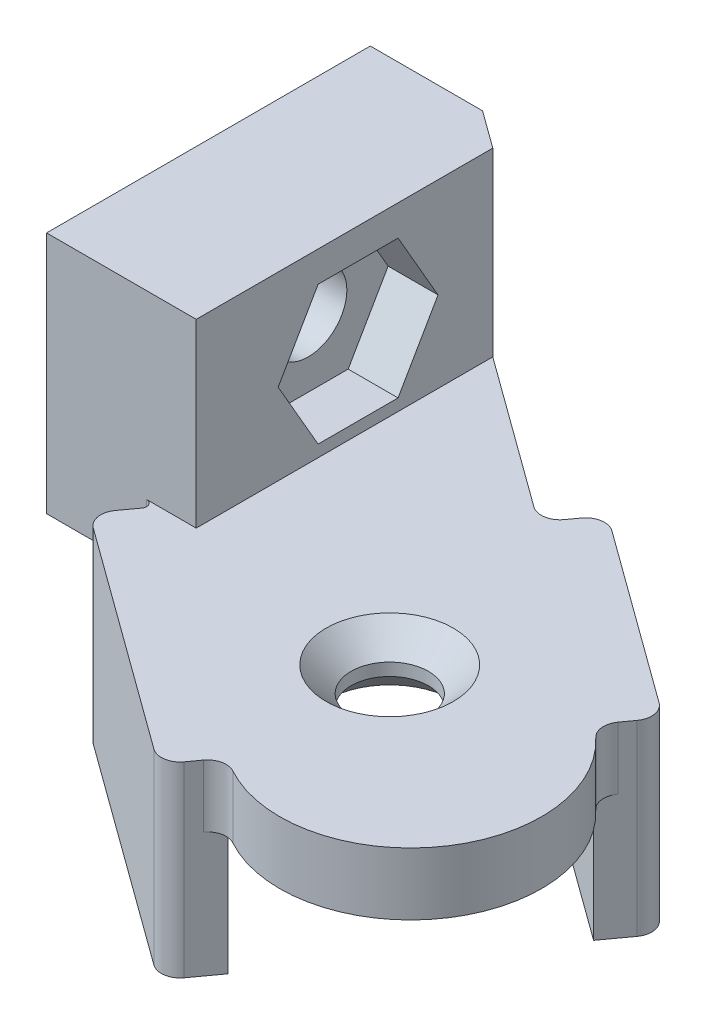
SolidWorks part; units mm, degrees
material "PA 类型 6"
ref_plane "前视基准面" through (0, 0, 0) normal (0, 0, 1) x (1, 0, 0)
ref_plane "上视基准面" through (0, 0, 0) normal (0, 1, 0) x (1, 0, 0)
ref_plane "右视基准面" through (0, 0, 0) normal (1, 0, 0) x (0, 0, -1)
sketch "草图1" plane through (0, 0, 0) normal (0, 1, 0) x (1, 0, 0)
  line L0 (0, 0) -> (0, 12.2017) construction
  line L1 (0, 0) -> (15.21, 0) construction
  line L2 (0, 0) -> (11.3188, 8.2236) construction
  line L5 (6.1542, 2.018) -> (-0.0175, -6.4766) construction
  line L7 (-10.1244, 13.8452) -> (6.1542, 2.018)
  line L8 (-10.1244, 0.8664) -> (-0.0175, -6.4766)
  line L9 (-10.1244, 13.8452) -> (-10.1244, 0.8664)
  line L10 (0, 0) -> (-11.3188, 8.2236) construction
  circle A0 centre (0, 0) radius 1.55
  arc A2 (6.1542, 2.018) -> (-0.0175, -6.4766) centre (3.0684, -2.2293) cw
  dimension "D1" = 3.1
  dimension "D5" = 5.25
  dimension "D2" = 36
  dimension "D6" = 10.1244
  dimension "D7" = 5.25
extrude "基座" add sketch "草图1" along normal blind 2.5
sketch "草图2" plane through (0, 0, 0) normal (0, 1, 0) x (1, 0, 0)
  line L3 (6.1542, 2.018) -> (-10.1244, 13.8452) construction
  line L5 (0, 0) -> (19.4408, 0) construction
  line L6 (6.1542, 2.018) -> (-10.1244, 13.8452) construction
  line L7 (0, 0) -> (0, 16.8119) construction
  line L14 (0, 0) -> (-14.65, 10.6439) construction
  line L15 (-11.3, -0.7516) -> (-10.1244, 0.8664)
  line L16 (-1.1931, -8.0947) -> (-11.3, -0.7516)
  line L17 (-0.0175, -6.4766) -> (-1.1931, -8.0947)
  line L18 (-10.1244, 0.8664) -> (-0.0175, -6.4766)
  line L19 (7.3298, 3.6361) -> (-0.8095, 9.5496)
  line L20 (6.1542, 2.018) -> (7.3298, 3.6361)
  line L21 (-1.9851, 7.9316) -> (6.1542, 2.018)
  line L22 (-0.8095, 9.5496) -> (-1.9851, 7.9316)
  point P6 (-1.9851, 7.9316)
  dimension "D1" = 36
  dimension "D2" = 2
extrude "机臂限位" add sketch "草图2" against normal blind 7.5 from surface contours L18 L15 L16 L17 | L19 L22 L21 L20 region at (-5.6587, 0, 3.6141) region at (2.6724, 0, -5.7838) starting at face at (-2.4662, 2.5, -1.7918)
sketch "草图3" plane through (0, 0, 0) normal (0, 1, 0) x (1, 0, 0)
  line L0 (-14.6244, 13.8452) -> (-10.1244, 13.8452)
  line L1 (-10.1244, 13.8452) -> (-10.1244, 0.8664)
  line L2 (-10.1244, 0.8664) -> (-14.6244, 0.8664)
  line L3 (-14.6244, 0.8664) -> (-14.6244, 13.8452)
  dimension "D1" = 4.5
extrude "限位-1" add sketch "草图3" along normal blind 9.75
sketch "草图4" plane through (0, 0, 0) normal (0, 0, 1) x (1, 0, 0)
  line L7 (-14.6244, 9.75) -> (-14.6244, 0) construction
  line L10 (-14.6244, 6.5) -> (-14.6244, 9.75)
  line L11 (-17.6244, 6.5) -> (-14.6244, 6.5)
  line L12 (-17.6244, -2.25) -> (-17.6244, 6.5)
  line L13 (-21.1244, -2.25) -> (-17.6244, -2.25)
  line L14 (-21.1244, 9.75) -> (-21.1244, -2.25)
  line L15 (-14.6244, 9.75) -> (-21.1244, 9.75)
  line L16 (-10.1244, 9.75) -> (-14.6244, 9.75) construction
  dimension "D5" = 3
  dimension "D6" = 3.5
  dimension "D7" = 3.25
  dimension "D8" = 8.75
chamfer "倒角1" distance 1 angle 45 2 edges at (0, 2.5, 1.55) (0, 0, 1.55)
fillet "圆角5" radius 0.75 7 edges at (-0.8095, -1.25, -9.5496) (7.3298, -1.25, -3.6361) (-1.1931, -1.25, 8.0947) (-11.3, -1.25, 0.7516) (-1.9851, 1.25, -7.9316) (6.1542, 1.25, -2.018) (-0.0175, 1.25, 6.4766)
sketch "草图5" plane through (-10.1244, 0, 0) normal (1, 0, 0) x (0, 0, -1)
  line L0 (0.8664, 9.75) -> (13.8452, 9.75) construction
  line L1 (10.5601, 5.75) -> (8.9579, 8.525)
  line L2 (8.9579, 8.525) -> (5.7537, 8.525)
  line L3 (5.7537, 8.525) -> (4.1515, 5.75)
  line L4 (4.1515, 5.75) -> (5.7537, 2.975)
  line L5 (5.7537, 2.975) -> (8.9579, 2.975)
  line L6 (8.9579, 2.975) -> (10.5601, 5.75)
  line L7 (7.3558, 15.1256) -> (7.3558, -0.4001) construction
  circle A0 centre (7.3558, 5.75) radius 2.775 construction
  point P12 (7.3558, 9.75)
  dimension "D1" = 5.55
  dimension "D2" = 4
extrude "切除-拉伸1" cut sketch "草图5" against normal blind 2
sketch "草图7" plane through (-10.1244, 0, 0) normal (1, 0, 0) x (0, 0, -1)
  line L0 (8.9579, 8.525) -> (5.7537, 8.525) construction
  circle A0 centre (7.3558, 5.75) radius 1.55
  point P7 (7.3558, 8.525)
  dimension "D1" = 3.1
extrude "切除-拉伸2" cut sketch "草图7" against normal up to surface (4.5 mm away) up to face at (-14.6244, 4.875, -7.3558)
sketch "草图8" plane through (0, 0, 0) normal (0, 1, 0) x (1, 0, 0)
  line L0 (-10.1244, 13.8452) -> (-8.6244, 12.7553)
  line L1 (-2.5918, 8.3724) -> (-10.1244, 13.8452) construction
  line L2 (-8.6244, 12.7553) -> (-8.6244, 0.8664)
  line L3 (-8.6244, 0.8664) -> (-10.1244, 0.8664)
  line L4 (-10.1244, 0.8664) -> (-10.1244, 13.8452)
  dimension "D1" = 1.5
extrude "结构补强修改" add sketch "草图8" along normal up to surface (9.75 mm away) from surface up to face at (-12.3744, 9.75, -7.3558) starting at face at (0, 2.5, -2.55)
sketch "草图9" plane through (-12.1244, 0, 0) normal (1, 0, 0) x (0, 0, -1)
  line L0 (8.9579, 8.525) -> (5.7537, 8.525) construction
  line L1 (8.9579, 2.975) -> (10.5601, 5.75)
  line L2 (10.5601, 5.75) -> (8.9579, 8.525)
  line L3 (8.9579, 8.525) -> (5.7537, 8.525)
  line L4 (5.7537, 8.525) -> (4.1515, 5.75)
  line L5 (4.1515, 5.75) -> (5.7537, 2.975)
  line L6 (5.7537, 2.975) -> (8.9579, 2.975)
  circle A0 centre (7.3558, 5.75) radius 2.775 construction
  circle A1 centre (7.3558, 5.75) radius 1.55 construction
  circle A2 centre (7.3558, 5.75) radius 1.55
  circle A3 centre (7.3558, 5.75) radius 1.55 construction
extrude "结构补强螺母位-1" cut sketch "草图5<2>" along normal through all
sketch "草图5<2>" plane through (-10.1244, 0, 0) normal (1, 0, 0) x (0, 0, -1) same geometry as "草图5"
extrude "结构补强螺母位-2" add sketch "草图9" along normal blind 1.5
fillet "圆角6" radius 0.25 1 edges at (-10.1244, 1.25, -0.8664)
